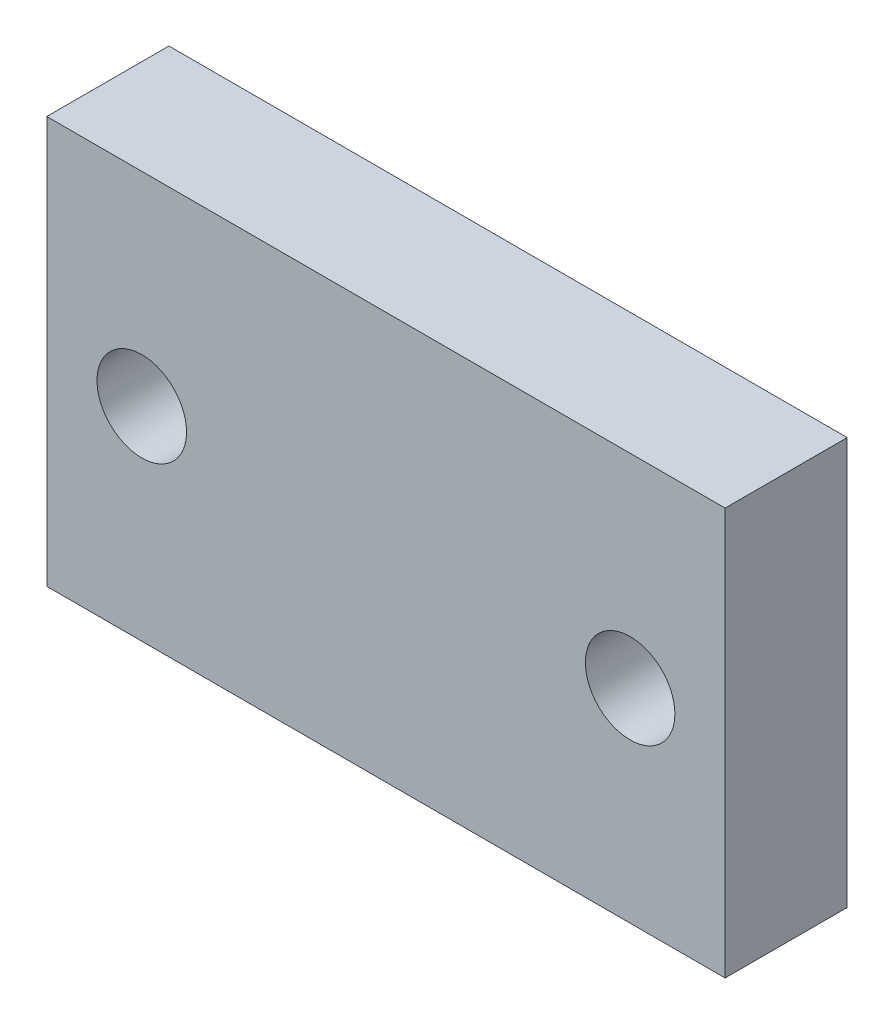
SolidWorks part; units mm, degrees
material "6061-T6 (SS)"
ref_plane "Front Plane" through (0, 0, 0) normal (0, 0, 1) x (1, 0, 0)
ref_plane "Top Plane" through (0, 0, 0) normal (0, 1, 0) x (1, 0, 0)
ref_plane "Right Plane" through (0, 0, 0) normal (1, 0, 0) x (0, 0, -1)
sketch "Sketch2" plane through (0, 0, 0) normal (0, 0, 1) x (1, 0, 0)
  line L1 (0, 0) -> (50, 0)
  line L2 (0, 0) -> (0, 30)
  line L3 (0, 30) -> (50, 30)
  line L4 (50, 0) -> (50, 30)
  dimension "D1" = 50
  dimension "D2" = 30
extrude "base" add sketch "Sketch2" along normal blind 9
hole_wizard "M6 Clearance Hole1" positions "Sketch3" profile "Sketch4" hole size "M6" standard "ANSI Metric" end condition through all
sketch "Sketch3" plane through (0, 0, 9) normal (0, 0, 1) x (1, 0, 0)
  line L0 (7, 15) -> (43, 15)
  line L2 (25, 15) -> (25, 30)
  line L3 (50, 30) -> (0, 30) construction
  line L5 (7, 15) -> (0, 15)
  line L6 (0, 30) -> (0, 0) construction
  point P0 (7, 15)
  point P2 (43, 15)
  dimension "D1" = 36
sketch "Sketch4" plane through (7, 15, 9) normal (1, 0, 0) x (0, -1, 0)
  line L0 (0, 0) -> (0, 9)
  line L1 (0, 9) -> (3.3, 9)
  line L2 (3.3, 9) -> (3.3, 0)
  line L5 (3.3, 0) -> (0, 0)
  line L11 (0, -6.35) -> (0, 107.95) construction
  dimension "Thru Hole Dia." = 6.6
  dimension "Thru Hole Depth" = 9
